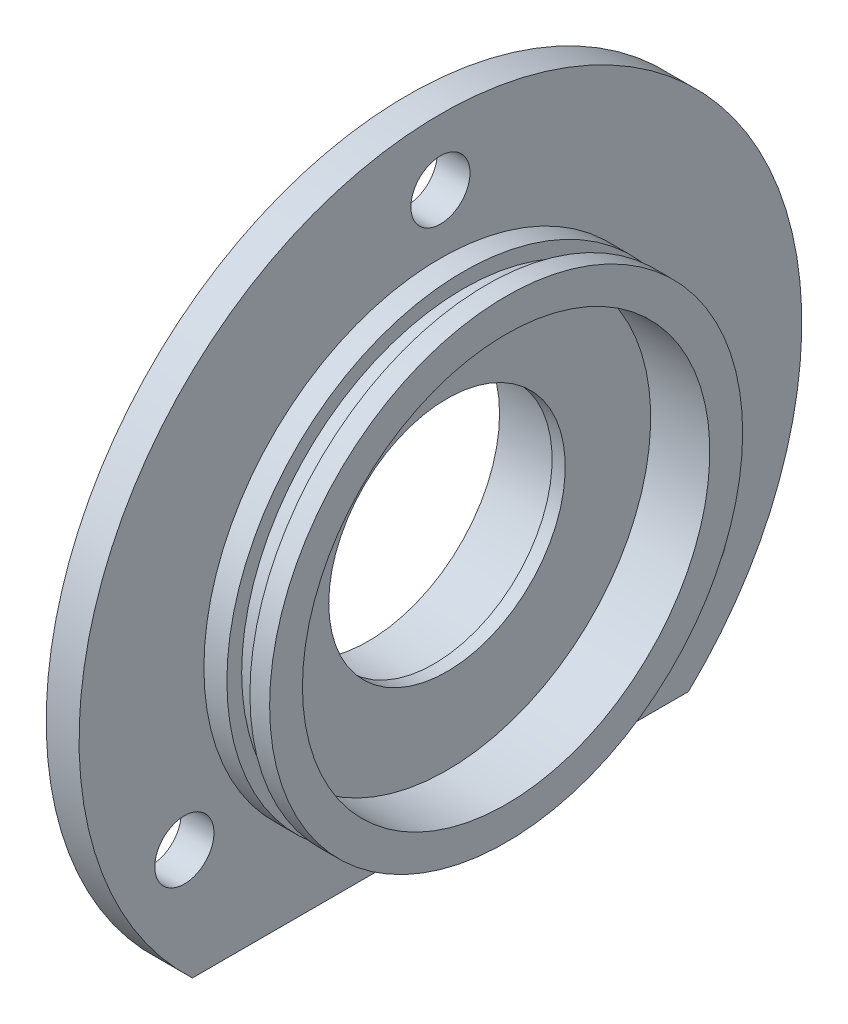
SolidWorks part; units mm, degrees
ref_plane "Piano frontale" through (0, 0, 0) normal (0, 0, 1) x (1, 0, 0)
ref_plane "Piano superiore" through (0, 0, 0) normal (0, 1, 0) x (1, 0, 0)
ref_plane "Piano destro" through (0, 0, 0) normal (1, 0, 0) x (0, 0, -1)
sketch "Schizzo1" plane through (0, 0, 0) normal (0, 0, 1) x (1, 0, 0)
  line L0 (0, 0) -> (0, 5)
  line L1 (0, 5) -> (6, 5)
  line L2 (6, 5) -> (6, 35)
  line L3 (6, 35) -> (11, 35)
  line L4 (11, 35) -> (11, 16)
  line L5 (11, 16) -> (14.5, 16)
  line L6 (21, 16) -> (21, 11)
  line L7 (21, 11) -> (12, 11)
  line L8 (12, 11) -> (12, -2)
  line L9 (12, -2) -> (10, -2)
  line L10 (10, -2) -> (10, 0)
  line L11 (10, 0) -> (0, 0)
  line L12 (-8.3068, -20) -> (27.2464, -20) construction
  line L13 (14.5, 16) -> (14.5, 13.75)
  line L14 (14.5, 13.75) -> (18, 13.75)
  line L15 (18, 13.75) -> (18, 16)
  line L16 (18, 16) -> (21, 16)
  dimension "D1" = 0
  dimension "D2" = 0
  dimension "D3" = 20
  dimension "D4" = 6
  dimension "10" = 10
  dimension "D5" = 5
  dimension "D6" = 55
  dimension "D7" = 5
  dimension "D8" = 36
  dimension "D9" = 31
  dimension "D10" = 10
  dimension "D11" = 2
  dimension "D12" = 18
  dimension "D13" = 33.75
  dimension "D14" = 3.5
  dimension "D15" = 3
revolve "Rivoluzione1" add sketch "Schizzo1" angle 360 about L12
sketch "Schizzo2" plane through (11, 0, 0) normal (1, 0, 0) x (0, 0, -1)
  line L0 (0, 25) -> (0, -20) construction
  line L1 (0, -20) -> (-38.9711, -42.5) construction
  line L2 (0, -20) -> (38.9711, -42.5) construction
  circle A0 centre (0, 25) radius 4.5
  circle A1 centre (0, -20) radius 36 construction
  circle A2 centre (88.3346, -128) radius 4.5
  circle A3 centre (-88.3346, -128) radius 4.5
  circle A4 centre (38.9711, -42.5) radius 4.5
  circle A5 centre (-38.9711, -42.5) radius 4.5
  circle A6 centre (0, -20) radius 55 construction
  point P11 (0, -77)
  point P16 (0, -20)
  dimension "D1" = 9
  dimension "D2" = 45
  dimension "D4" = 3
  dimension "D5" = 45
  dimension "D6" = 45
  dimension "D7" = 45
  dimension "D3" = 3
extrude "Taglio-Estrusione1" cut sketch "Schizzo2" against normal through all
sketch "Schizzo3" plane through (6, 0, 0) normal (-1, 0, 0) x (0, 0, 1)
  line L0 (-37.7492, -60) -> (37.7492, -60)
  line L1 (37.7492, -60) -> (37.7492, -90)
  line L2 (37.7492, -90) -> (-37.7492, -90)
  line L3 (-37.7492, -90) -> (-37.7492, -60)
  circle A0 centre (0, -20) radius 55 construction
  circle A1 centre (0, -20) radius 18 construction
  dimension "D1" = 40
  dimension "D2" = 30
extrude "Taglio-Estrusione2" cut sketch "Schizzo3" against normal through all
ref_axis "Assi1" through (10, -20, 0) along (-1, 0, 0)
